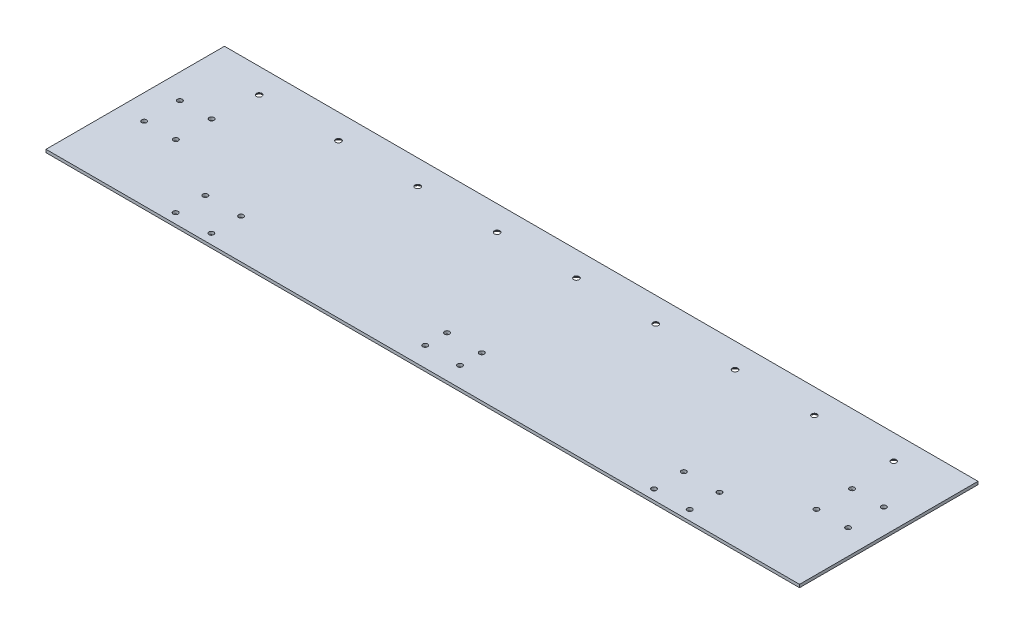
SolidWorks part; units mm, degrees
ref_plane "Front Plane" through (0, 0, 0) normal (0, 0, 1) x (1, 0, 0)
ref_plane "Top Plane" through (0, 0, 0) normal (0, 1, 0) x (1, 0, 0)
ref_plane "Right Plane" through (0, 0, 0) normal (1, 0, 0) x (0, 0, -1)
sketch "Sketch1" plane through (0, 0, 0) normal (0, 1, 0) x (1, 0, 0)
  line L1 (-380, 90) -> (380, 90)
  line L2 (-380, 90) -> (-380, -90)
  line L3 (-380, -90) -> (380, -90)
  line L4 (380, 90) -> (380, -90)
  line L5 (-380, 90) -> (380, -90) construction
  line L6 (-380, -90) -> (380, 90) construction
  point P0 (0, 0)
  dimension "D1" = 760
  dimension "D2" = 180
extrude "Boss-Extrude1" add sketch "Sketch1" along normal blind 3
hole_wizard "CSK for M5 Countersunk Flat Head Screw1" positions "Sketch2" profile "Sketch3" countersink size "M5" standard "ISO" end condition through all
sketch "Sketch2" plane through (0, 0, 0) normal (0, -1, 0) x (-1, 0, 0)
  line L0 (-380, 90) -> (380, 90) construction
  point P0 (0, 65)
  point P13 (80, 65)
  point P14 (160, 65)
  point P15 (240, 65)
  point P16 (320, 65)
  point P23 (-80, 65)
  point P24 (-160, 65)
  point P25 (-240, 65)
  point P26 (-320, 65)
  dimension "D1" = 25
  dimension "D2" = 5
  dimension "D3" = 5
sketch "Sketch3" plane through (0, 0, -65) normal (1, 0, 0) x (0, 0, -1)
  line L0 (0, 0) -> (0, 3)
  line L1 (0, 3) -> (2.75, 3)
  line L2 (2.75, 3) -> (2.75, 2.45)
  line L3 (2.75, 2.45) -> (5.2, 0)
  line L5 (5.2, 0) -> (0, 0)
  line L6 (-2.75, 2.45) -> (-5.2, 0) construction
  line L11 (0, -6.35) -> (0, 107.95) construction
  dimension "Thru Hole Dia." = 5.5
  dimension "Thru Hole Depth" = 3
  dimension "Near C'Sink Dia." = 10.4
  dimension "Near C'Sink Angle" = 90
sketch "Sketch4" plane through (0, 3, 0) normal (0, 1, 0) x (1, 0, 0)
  line L0 (380, 90) -> (-380, 90) construction
  line L1 (0, 0) -> (0, -90) construction
  line L2 (-380, 90) -> (-380, -90) construction
  line L3 (-380, -90) -> (380, -90) construction
  circle A0 centre (-259.25, -80) radius 2.5
  circle A1 centre (-223.25, -80) radius 2.5
  circle A2 centre (-259.25, -50) radius 2.5
  circle A3 centre (-223.25, -50) radius 2.5
  circle A4 centre (259.25, -80) radius 2.5
  circle A5 centre (223.25, -80) radius 2.5
  circle A6 centre (223.25, -50) radius 2.5
  circle A7 centre (259.25, -50) radius 2.5
  dimension "D1" = 5
  dimension "D2" = 36
  dimension "D3" = 170
  dimension "D4" = 120.75
  dimension "D5" = 30
extrude "Cut-Extrude1" cut sketch "Sketch4" against normal blind 10
sketch "Sketch5" plane through (0, 3, 0) normal (0, 1, 0) x (1, 0, 0)
  line L0 (-380, 90) -> (-380, -90) construction
  line L1 (380, 90) -> (-380, 90) construction
  line L2 (0, 0) -> (0, 90) construction
  circle A0 centre (-355, 20) radius 2.5
  circle A1 centre (-323, 20) radius 2.5
  circle A2 centre (-355, -16) radius 2.5
  circle A3 centre (-323, -16) radius 2.5
  circle A4 centre (323, 20) radius 2.5
  circle A5 centre (323, -16) radius 2.5
  circle A6 centre (355, -16) radius 2.5
  circle A7 centre (355, 20) radius 2.5
  dimension "D1" = 5
  dimension "D2" = 32
  dimension "D3" = 36
  dimension "D4" = 25
  dimension "D5" = 70
extrude "Cut-Extrude2" cut sketch "Sketch5" against normal blind 10
sketch "Sketch6" plane through (0, 3, 0) normal (0, 1, 0) x (1, 0, 0)
  line L0 (0, 0) -> (0, -90) construction
  line L1 (-380, -90) -> (380, -90) construction
  circle A0 centre (-17.5, -48) radius 2.5
  circle A1 centre (-17.5, -70) radius 2.5
  circle A2 centre (17.5, -70) radius 2.5
  circle A3 centre (17.5, -48) radius 2.5
  point P9 (0, 0)
  dimension "D1" = 5
  dimension "D2" = 22
  dimension "D3" = 20
  dimension "D4" = 17.5
extrude "Cut-Extrude3" cut sketch "Sketch6" against normal blind 8
